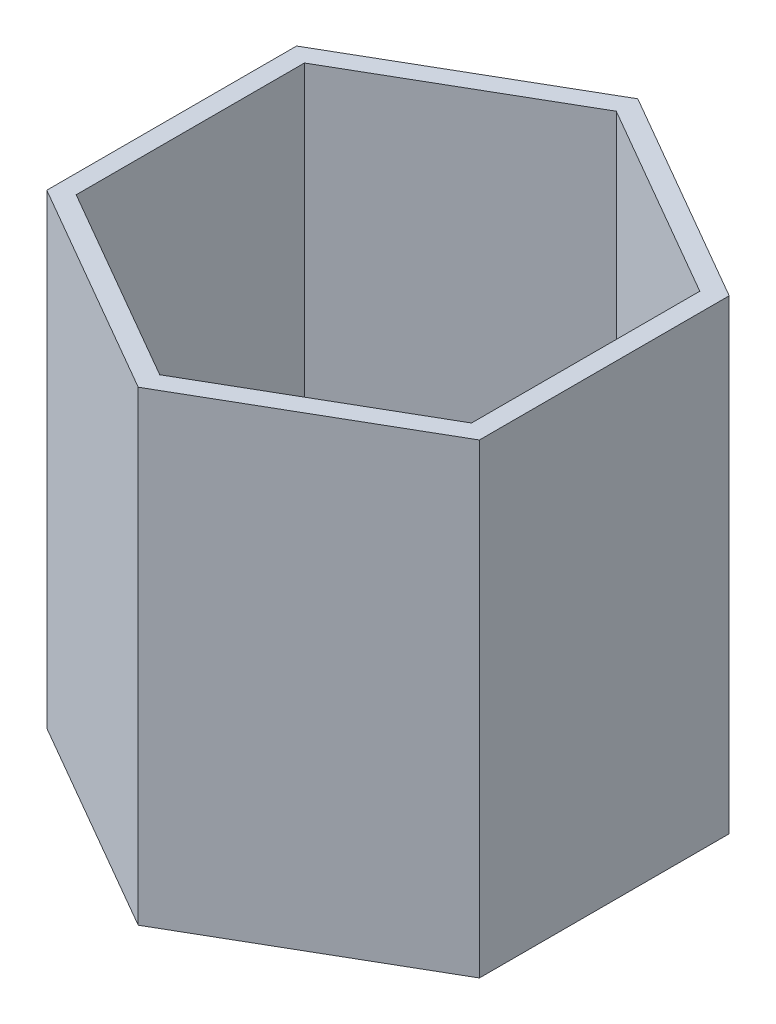
SolidWorks part; units mm, degrees
ref_plane "Front Plane" through (0, 0, 0) normal (0, 0, 1) x (1, 0, 0)
ref_plane "Top Plane" through (0, 0, 0) normal (0, 1, 0) x (1, 0, 0)
ref_plane "Right Plane" through (0, 0, 0) normal (1, 0, 0) x (0, 0, -1)
sketch "Sketch1" plane through (0, 0, 0) normal (0, 1, 0) x (1, 0, 0)
  line L0 (0, 26.8034) -> (-23.2125, 13.4017)
  line L1 (21.2125, 12.247) -> (0, 24.494)
  line L2 (0, 24.494) -> (-21.2125, 12.247)
  line L3 (-21.2125, 12.247) -> (-21.2125, -12.247)
  line L4 (-21.2125, -12.247) -> (0, -24.494)
  line L5 (0, -24.494) -> (21.2125, -12.247)
  line L6 (21.2125, -12.247) -> (21.2125, 12.247)
  line L7 (-23.2125, 13.4017) -> (-23.2125, -13.4017)
  line L8 (-23.2125, -13.4017) -> (0, -26.8034)
  line L9 (0, -26.8034) -> (23.2125, -13.4017)
  line L10 (23.2125, -13.4017) -> (23.2125, 13.4017)
  line L11 (23.2125, 13.4017) -> (0, 26.8034)
  circle A0 centre (0, 0) radius 21.2125 construction
  point P9 (0, 0)
  point P15 (23.5934, 7.2016)
  point P16 (0, 0)
  point P17 (-27.6122, -1.8744)
  point P18 (0, 0)
  point P22 (-21.2672, -12.1516)
  point P23 (0, 0)
  dimension "D2" = 42.4249
  dimension "D1" = 2
extrude "Boss-Extrude2" add sketch "Sketch1" along normal blind 3 contours L5 L6 L1 L2 L3 L4 | L10 L11 L0 L7 L8 L9 L6 L5 L4 L3 L2 L1 region at (11.2517, 0, -19.4884) region at (0, 0, 0)
extrude "Boss-Extrude3" add sketch "Sketch1<4>" along normal blind 50
sketch "Sketch1<4>" plane through (0, 0, 0) normal (0, 1, 0) x (1, 0, 0) same geometry as "Sketch1"
ref_plane "Plane1" through (0, 0, -26.8034) normal (0, 0, 1) x (1, 0, 0)
sketch "Sketch2" plane through (0, 0, -26.8034) normal (0, 0, 1) x (1, 0, 0)
  line L0 (17.4584, 50) -> (17.4584, 48.1358)
  line L1 (23.2125, 50) -> (0, 50) construction
  line L2 (17.4584, 48.1358) -> (21.1348, 48.1358)
  line L3 (21.1348, 48.1358) -> (21.1348, 46.1101)
  line L4 (21.1348, 46.1101) -> (-19.9057, 46.1101)
  line L5 (-19.9057, 46.1101) -> (-19.9057, 48.1358)
  line L6 (-19.9057, 48.1358) -> (-16.6045, 48.1358)
  line L7 (-16.6045, 48.1358) -> (-16.6045, 50)
  line L8 (0, 50) -> (-23.2125, 50) construction
  line L9 (17.4584, 50) -> (-16.6045, 50)
